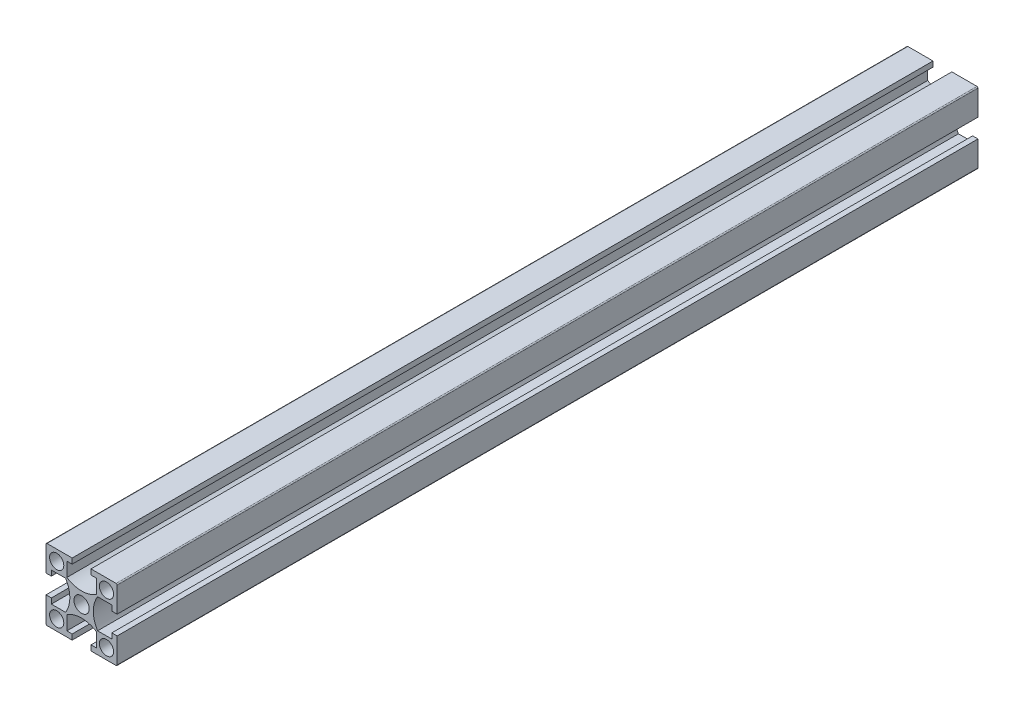
SolidWorks part; units mm, degrees
material "3.0255 (EN-AW 1350A)"
ref_plane "정면" through (0, 0, 0) normal (0, 0, 1) x (1, 0, 0)
ref_plane "윗면" through (0, 0, 0) normal (0, 1, 0) x (1, 0, 0)
ref_plane "우측면" through (0, 0, 0) normal (1, 0, 0) x (0, 0, -1)
sketch "스케치1" plane through (0, 0, 0) normal (0, 0, 1) x (1, 0, 0)
  line L0 (0, 32.0265) -> (0, -31.6588) construction
  line L1 (-10, 10) -> (-10, -10)
  line L2 (-10, 10) -> (10, 10)
  line L3 (-10, 2.65) -> (-8.5, 2.65)
  line L4 (13.6618, 0) -> (-11.6993, 0) construction
  line L5 (-8.5, 2.65) -> (-8.5, 4.15)
  line L6 (-8.5, 4.15) -> (-4.5032, 4.15)
  line L7 (-10, -2.65) -> (-8.5, -2.65)
  line L8 (-8.5, -2.65) -> (-8.5, -4.15)
  line L9 (-8.5, -4.15) -> (-4.5032, -4.15)
  line L10 (-10, -10) -> (10, -10)
  line L11 (10, 10) -> (10, -10)
  circle A0 centre (-7, 7) radius 2
  circle A1 centre (-7, -7) radius 2
  arc A2 (-4.5032, 4.15) -> (-4.5032, -4.15) centre (-11.0587, 0) cw
  circle A3 centre (0, 0) radius 2.15
  circle A4 centre (7, 7) radius 2
  circle A5 centre (7, -7) radius 2
  point P21 (-10, 0)
  point P23 (-3.3, 0)
  point P31 (0, -10)
  point P32 (0, 10)
  dimension "D3" = 4
  dimension "D9" = 6.7
  dimension "D10" = 4.3
  dimension "D11" = 7.7587
  dimension "D1" = 20
  dimension "D2" = 20
  dimension "D4" = 14
  dimension "D5" = 14
  dimension "D6" = 5.3
  dimension "D7" = 8.3
  dimension "D8" = 1.5
extrude "보스-돌출1" add sketch "스케치1" along normal blind 242 contours A0 | A4 | A3 | A5 | A1 | A2 L6 L5 L3 L1 L7 L8 L9 | L2 L11 L10 L1 region at (-6.6069, 0, 0) region at (-7, 7, 0) region at (-7, -7, 0) region at (0, 0, 0) region at (7, 7, 0) region at (7, -7, 0)
extrude "컷-돌출1" cut sketch "스케치1<3>" along normal up to next contours A2 L6 L5 L3 L1 L7 L8 L9 region at (-6.6069, 0, 0)
sketch "스케치1<3>" plane through (0, 0, 0) normal (0, 0, 1) x (1, 0, 0) same geometry as "스케치1"
pattern_circular "원형 패턴1" count 4 over 360 about axis through (0, 0, 242) along (0, 0, -1) of "컷-돌출1" reverse direction yes
fillet "필렛1" radius 0.3 4 edges at (10, -10, 121) (-10, -10, 121) (-10, 10, 121) (10, 10, 121)
sketch "스케치2" plane through (0, 10, 0) normal (0, 1, 0) x (1, 0, 0)
  line L0 (-9.7, -20) -> (9.7, -20) construction
  line L1 (-9.7, 0) -> (-9.7, -242) construction
  line L2 (9.7, -242) -> (9.7, 0) construction
  line L3 (4.15, 0) -> (-4.15, 0) construction
  circle A0 centre (0, -231) radius 2.5
  circle A1 centre (0, -31) radius 2.5
  dimension "D1" = 11
  dimension "D3" = 11
  dimension "D2" = 20
extrude "컷-돌출2" cut sketch "스케치2" against normal through all
